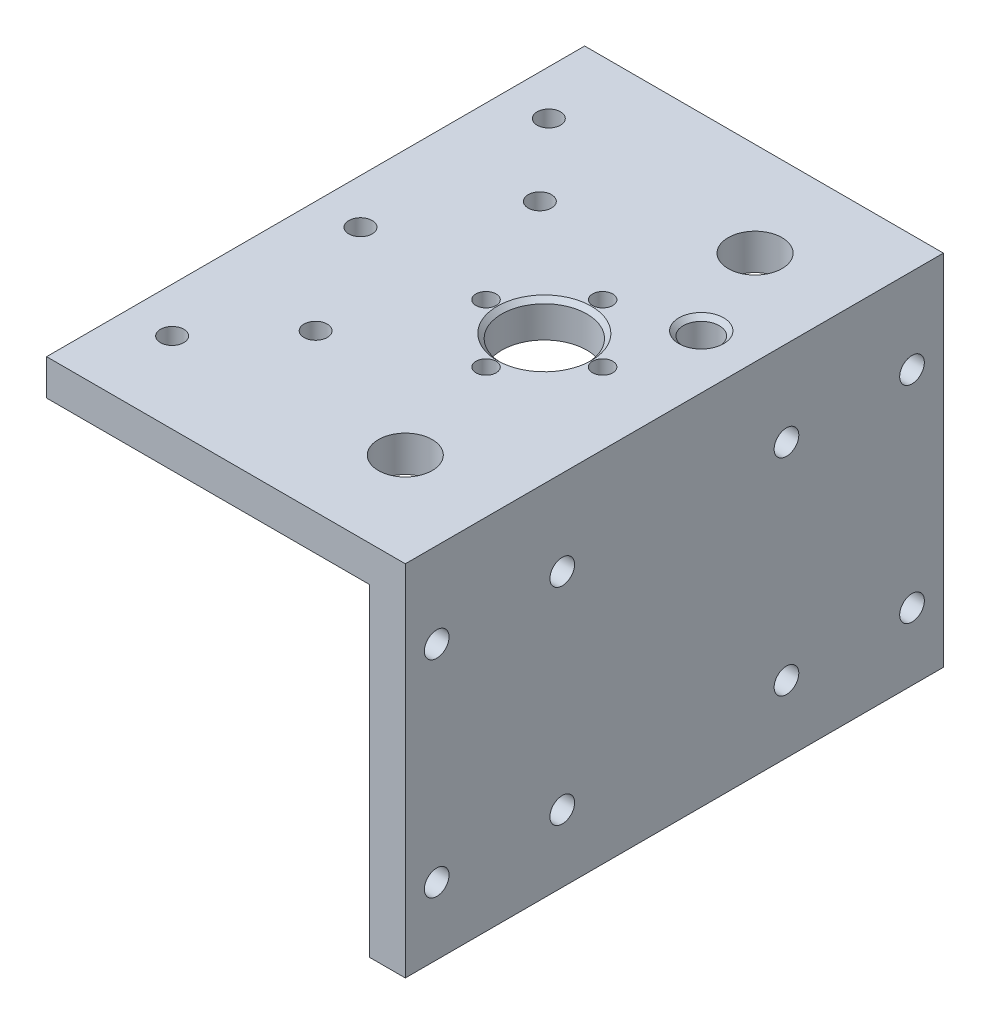
SolidWorks part; units mm, degrees
material "Lega 1060"
ref_plane "Piano frontale" through (0, 0, 0) normal (0, 0, 1) x (1, 0, 0)
ref_plane "Piano superiore" through (0, 0, 0) normal (0, 1, 0) x (1, 0, 0)
ref_plane "Piano destro" through (0, 0, 0) normal (1, 0, 0) x (0, 0, -1)
sketch "Schizzo1" plane through (0, 0, 0) normal (0, 0, 1) x (1, 0, 0)
  line L0 (0, 0) -> (-80, 0)
  line L1 (-80, 0) -> (-80, -8)
  line L2 (-80, -8) -> (-8, -8)
  line L3 (-8, -8) -> (-8, -80)
  line L4 (-8, -80) -> (0, -80)
  line L5 (0, -80) -> (0, 0)
  dimension "D1" = 80
  dimension "D2" = 80
  dimension "D3" = 8
  dimension "D4" = 8
extrude "Estrusione-Estrusione1" add sketch "Schizzo1" along normal blind 120
sketch "Schizzo12" plane through (0, 0, 0) normal (1, 0, 0) x (0, 0, -1)
  line L0 (0, -8) -> (-120, -8) construction
  line L1 (-21, 0) -> (-21, 18.8536) construction
  line L5 (0, -80) -> (0, 0) construction
  line L6 (-120, -80) -> (-120, 0) construction
  line L7 (-120, 0) -> (0, 0) construction
  line L8 (-113, -19) -> (10.4492, -19) construction
  line L9 (-113, -65) -> (16.1501, -65) construction
  line L10 (-99, -47.4454) -> (-99, 40.839) construction
  circle A0 centre (-113, -19) radius 2.75
  circle A1 centre (-85, -19) radius 2.75
  circle A6 centre (-35, -19) radius 2.75
  circle A7 centre (-7, -19) radius 2.75
  circle A10 centre (-85, -65) radius 2.75
  circle A11 centre (-113, -65) radius 2.75
  circle A12 centre (-7, -65) radius 2.75
  circle A13 centre (-35, -65) radius 2.75
  dimension "D1" = 5.5
  dimension "D5" = 28
  dimension "D6" = 28
  dimension "D7" = 28
  dimension "D8" = 28
  dimension "D2" = 8
  dimension "D3" = 11
  dimension "D4" = 57
  dimension "D9" = 21
  dimension "D10" = 21
sketch "Schizzo6" plane through (0, 0, 0) normal (0, 1, 0) x (1, 0, 0)
  line L0 (-21, -0.5808) -> (-21, -110.5835) construction
  line L2 (0, 0) -> (-80, 0) construction
  line L3 (-32.5218, -60) -> (-8.0464, -60) construction
  line L6 (0, -120) -> (-80, -120) construction
  circle A0 centre (-21, -21) radius 6
  circle A1 centre (-21, -99) radius 6
  dimension "D2" = 12
  dimension "D1" = 13
  dimension "D3" = 21
extrude "Taglio-Estrusione2" cut sketch "Schizzo6" against normal up to next
sketch "Schizzo7" plane through (0, 0, 0) normal (0, 1, 0) x (1, 0, 0)
  line L0 (-53.636, -60) -> (3.6289, -60) construction
  line L1 (0, -120) -> (-80, -120) construction
  line L2 (0, 0) -> (-80, 0) construction
  line L3 (-21, -21) -> (-21, -99) construction
  line L4 (0, -120) -> (0, 0) construction
  circle A0 centre (-29, -60) radius 9.5
  circle A1 centre (-12, -42) radius 4
  dimension "D1" = 19
  dimension "D2" = 8
  dimension "D3" = 8
  dimension "D4" = 12
  dimension "D5" = 42
extrude "Taglio-Estrusione3" cut sketch "Schizzo7" against normal up to next
hole_wizard "Foro per Vite M4-2" positions "Schizzo9" profile "Schizzo8" hole size "M4" standard "ISO" end condition through all
sketch "Schizzo9" plane through (0, 0, 0) normal (0, 1, 0) x (1, 0, 0)
  line L0 (-18.4657, -60) -> (-16, -60) construction
  line L2 (-29, -57.7684) -> (-29, -66.5063) construction
  circle A2 centre (-29, -60) radius 9.5 construction
  point P0 (-29, -47)
  point P2 (-42, -60)
  point P4 (-29, -73)
  point P8 (-16, -60)
  point P20 (-29, -60)
  dimension "D1" = 26
  dimension "D2" = 13
  dimension "D3" = 13
sketch "Schizzo8" plane through (-29, 0, 47) normal (1, 0, 0) x (0, 0, 1)
  line L0 (0, 0) -> (0, 80)
  line L1 (0, 80) -> (2.25, 80)
  line L2 (2.25, 80) -> (2.25, 0)
  line L5 (2.25, 0) -> (0, 0)
  line L11 (0, -6.35) -> (0, 107.95) construction
  dimension "Thru Hole Dia." = 4.5
  dimension "Thru Hole Depth" = 80
extrude "Taglio-Estrusione4" cut sketch "Schizzo12" against normal blind 10
sketch "Schizzo14" plane through (0, 0, 0) normal (0, 1, 0) x (1, 0, 0)
  line L0 (-70, 0) -> (-70, -120) construction
  line L1 (0, 0) -> (-80, 0) construction
  line L2 (0, -120) -> (-80, -120) construction
  line L3 (-80, -120) -> (-80, 0) construction
  line L4 (-55, 0) -> (-55, -120) construction
  line L5 (-21, -99) -> (-80, -99) construction
  line L6 (-80, -60) -> (0, -60) construction
  line L7 (0, -120) -> (0, 0) construction
  line L8 (-21, -21) -> (-80, -21) construction
  circle A0 centre (-70, -18) radius 2.6
  circle A1 centre (-70, -60) radius 2.6
  circle A2 centre (-70, -102) radius 2.6
  circle A3 centre (-55, -35) radius 2.6
  circle A4 centre (-55, -85) radius 2.6
  dimension "D3" = 5.2
  dimension "D4" = 5.2
  dimension "D5" = 5.2
  dimension "D6" = 5.2
  dimension "D7" = 5.2
  dimension "D1" = 10
  dimension "D2" = 25
  dimension "D8" = 35
  dimension "D9" = 35
extrude "Taglio-Estrusione5" cut sketch "Schizzo14" against normal blind 10
chamfer "Smusso1" distance 1 angle 45 1 edges at (-16, 0, 42)
chamfer "Smusso2" distance 1 angle 45 1 edges at (-38.5, 0, 60)
